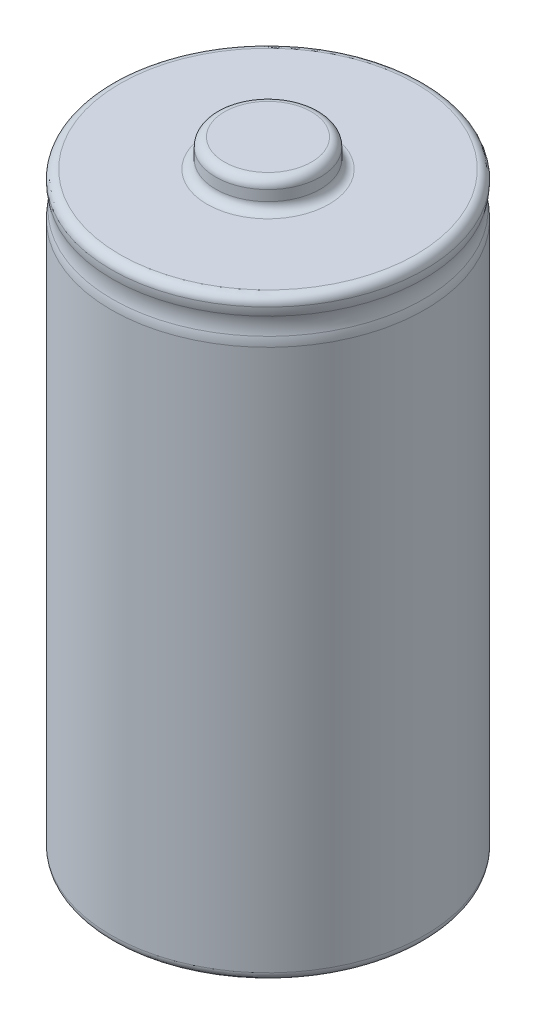
SolidWorks part; units mm, degrees
ref_plane "Front Plane" through (0, 0, 0) normal (0, 0, 1) x (1, 0, 0)
ref_plane "Top Plane" through (0, 0, 0) normal (0, 1, 0) x (1, 0, 0)
ref_plane "Right Plane" through (0, 0, 0) normal (1, 0, 0) x (0, 0, -1)
sketch "Sketch1" plane through (0, 0, 0) normal (0, 0, 1) x (1, 0, 0)
  line L0 (0, -17.85) -> (0, 17.85)
  line L1 (0, 17.85) -> (3, 17.85)
  line L2 (3, 17.85) -> (3, 16.25)
  line L3 (3, 16.25) -> (9, 16.25)
  line L4 (9, 16.25) -> (9, -17.85)
  line L5 (9, -17.85) -> (0, -17.85)
  dimension "D1" = 35.7
  dimension "D2" = 9
  dimension "D3" = 3
  dimension "D4" = 1.6
revolve "Revolve1" add sketch "Sketch1" angle 360 about L0
fillet "Fillet1" radius 0.5 4 edges at (0, 17.85, -3) (0, 16.25, -9) (0, 16.25, -3) (0, -17.85, -9)
sketch "Sketch2" plane through (0, 0, 0) normal (0, 0, 1) x (1, 0, 0)
  line L0 (0, 17.85) -> (0, -17.85)
  line L1 (2.5, 17.85) -> (-2.5, 17.85) construction
  line L2 (-9, -17.85) -> (9, -17.85) construction
  line L3 (9, -17.35) -> (9, 15.75) construction
  line L4 (9, 13.75) -> (9, 15.75)
  arc A0 (9, 15.75) -> (8.5, 16.25) centre (8.5, 15.75) ccw construction
  arc A1 (9, 15.75) -> (8.5, 16.25) centre (8.5, 15.75) ccw construction
  arc A2 (9, 15.75) -> (8.9365, 15.25) centre (7, 15.75) cw
  arc A3 (8.9365, 15.25) -> (8.9365, 14.25) centre (10.873, 14.75) ccw
  arc A4 (8.9365, 14.25) -> (9, 13.75) centre (7, 13.75) cw
  dimension "D1" = 2
  dimension "D2" = 2
revolve "Cut-Revolve1" cut sketch "Sketch2" angle 360 about L0 region at (8.9512, 14.75, 0)
